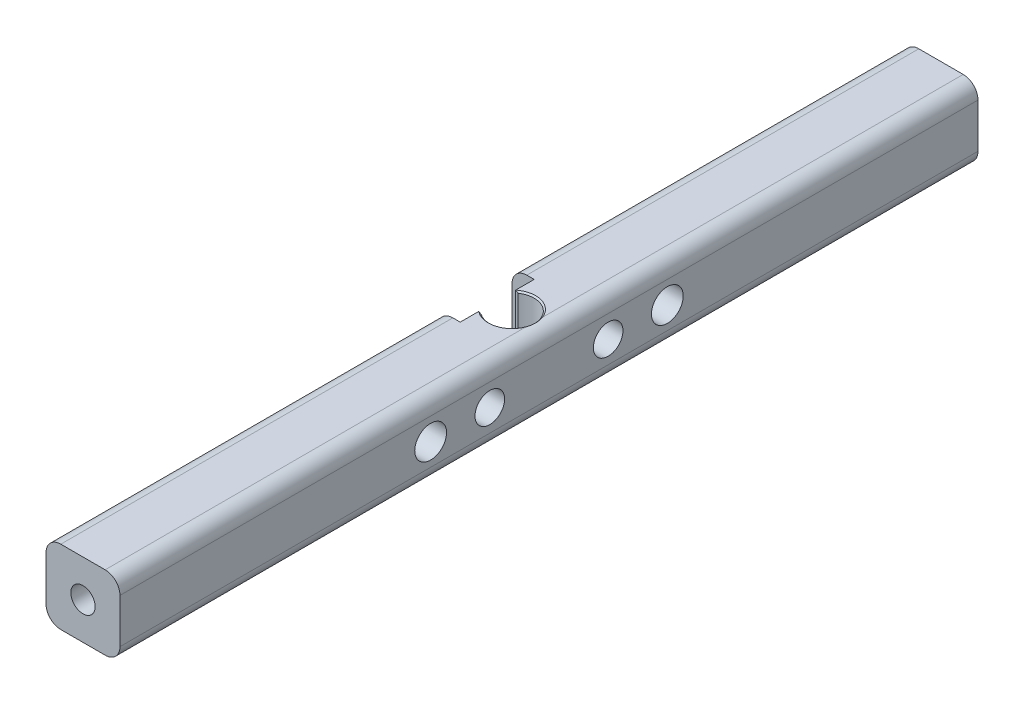
SolidWorks part; units mm, degrees
material "Alliage 1060"
ref_plane "Face" through (0, 0, 0) normal (0, 0, 1) x (1, 0, 0)
ref_plane "Dessus" through (0, 0, 0) normal (0, 1, 0) x (1, 0, 0)
ref_plane "Droite" through (0, 0, 0) normal (1, 0, 0) x (0, 0, -1)
sketch "Esquisse1" plane through (0, 0, 0) normal (0, 0, 1) x (1, 0, 0)
  line L1 (-5, 5) -> (5, 5)
  line L2 (-5, 5) -> (-5, -5)
  line L3 (-5, -5) -> (5, -5)
  line L4 (5, 5) -> (5, -5)
  dimension "D1" = 5
  dimension "D2" = 5
extrude "Boss.-Extru.1" add sketch "Esquisse1" along normal mid plane 116
sketch "Esquisse12" plane through (0, 5, 0) normal (0, 1, 0) x (1, 0, 0)
  circle A0 centre (0, 0) radius 3
extrude "Enlèv. mat.-Extru.2" cut sketch "Esquisse12" against normal up to next
chamfer "Chanfrein1" distance 0.2 angle 45 2 edges at (-3, 5, 0) (0, -5, 3)
fillet "Congé1" radius 2 4 edges at (-5, -5, 0) (5, -5, 0) (5, 5, 0) (-5, 5, 0)
hole_wizard "Trou taraudé M41" positions "Esquisse14" profile "Esquisse13" tap size "M4" standard "Iso"
sketch "Esquisse14" plane through (0, 0, 58) normal (0, 0, 1) x (1, 0, 0)
  point P0 (0, 0)
sketch "Esquisse13" plane through (0, 0, 58) normal (1, 0, 0) x (0, -1, 0)
  line L0 (0, 0) -> (0, 12.4914)
  line L1 (0, 12.4914) -> (1.65, 11.5)
  line L2 (1.65, 11.5) -> (1.65, 0)
  line L5 (1.65, 0) -> (0, 0)
  line L10 (0, 12.4914) -> (-1.65, 11.5) construction
  line L11 (0, -6.35) -> (0, 107.95) construction
  dimension "Diamètre du trou pour taraudage" = 3.3
  dimension "Profondeur du trou pour taraudage" = 11.5
  dimension "Angle de pointe" = 118
cosmetic thread "Filetage de perçage1" parameters "D1"=8, "D2"=4
hole_wizard "Trou taraudé M42" positions "Esquisse16" profile "Esquisse15" tap size "M4" standard "Iso"
sketch "Esquisse16" plane through (0, 0, -58) normal (0, 0, -1) x (-1, 0, 0)
  point P0 (0, 0)
sketch "Esquisse15" plane through (0, 0, -58) normal (1, 0, 0) x (0, 1, 0)
  line L0 (0, 0) -> (0, 12.4914)
  line L1 (0, 12.4914) -> (1.65, 11.5)
  line L2 (1.65, 11.5) -> (1.65, 0)
  line L5 (1.65, 0) -> (0, 0)
  line L10 (0, 12.4914) -> (-1.65, 11.5) construction
  line L11 (0, -6.35) -> (0, 107.95) construction
  dimension "Diamètre du trou pour taraudage" = 3.3
  dimension "Profondeur du trou pour taraudage" = 11.5
  dimension "Angle de pointe" = 118
cosmetic thread "Filetage de perçage2" parameters "D1"=8, "D2"=4
hole_wizard "Diamètre du perçage Ø5.0 (5)1" [suppressed] positions "Esquisse18" profile "Esquisse17" hole size "Ø5.0" standard "Din"
sketch "Esquisse18" plane through (-5, 0, 0) normal (-1, 0, 0) x (0, 0, 1)
  point P0 (0, 0)
sketch "Esquisse17" plane through (-5, 0, 0) normal (0, 1, 0) x (0, 0, 1)
  line L0 (0, 0) -> (0, 2)
  line L1 (0, 2) -> (2.6, 2)
  line L2 (2.6, 2) -> (2.6, 0)
  line L5 (2.6, 0) -> (0, 0)
  line L11 (0, -6.35) -> (0, 107.95) construction
  dimension "Diamètre du perçage jusqu'au prochain" = 5.2
  dimension "Profondeur du perçage jusqu'au prochain" = 2
hole_wizard "Diamètre du perçage Ø4.0 (4)1" positions "Esquisse20" profile "Esquisse19" hole size "Ø4.0" standard "Din"
sketch "Esquisse20" plane through (5, 0, 0) normal (1, 0, 0) x (0, 0, -1)
  point P0 (8, 0)
  point P2 (-8, 0)
  dimension "D1" = 8
  dimension "D2" = 8
sketch "Esquisse19" plane through (5, 0, -8) normal (0, 1, 0) x (0, 0, -1)
  line L0 (0, 0) -> (0, 6.2017)
  line L1 (0, 6.2017) -> (2, 5)
  line L2 (2, 5) -> (2, 0)
  line L5 (2, 0) -> (0, 0)
  line L10 (0, 6.2017) -> (-2, 5) construction
  line L11 (0, -6.35) -> (0, 107.95) construction
  dimension "Diamètre du perçage" = 4
  dimension "Profondeur du perçage" = 5
  dimension "Angle de pointe" = 118
hole_wizard "Chambrage pour vis à tête hexagonale M41" positions "Esquisse22" profile "Esquisse21" counterbore size "M4" standard "Iso" end condition through all
sketch "Esquisse22" plane through (-5, 0, 0) normal (-1, 0, 0) x (0, 0, 1)
  point P0 (-16, 0)
  point P2 (16, 0)
  dimension "D1" = 16
  dimension "D2" = 16
sketch "Esquisse21" plane through (-5, 0, -16) normal (0, 1, 0) x (0, 0, 1)
  line L0 (0, 0) -> (0, 10)
  line L1 (0, 10) -> (2.15, 10)
  line L3 (2.15, 10) -> (2.15, 4.4)
  line L4 (2.15, 4.4) -> (4, 4.4)
  line L5 (4, 4.4) -> (4, 0)
  line L7 (4, 0) -> (0, 0)
  line L11 (0, -6.35) -> (0, 107.95) construction
  dimension "Diamètre du perçage jusqu'au prochain" = 4.3
  dimension "Profondeur du perçage jusqu'au prochain" = 10
  dimension "Diamètre du chambrage" = 8
  dimension "Profondeur du chambrage" = 4.4
hole_wizard "Trou taraudé M31" positions "Esquisse24" profile "Esquisse23" tap size "M3" standard "Iso"
sketch "Esquisse24" plane through (-5, 0, 0) normal (-1, 0, 0) x (0, 0, 1)
  point P0 (-8, 0)
  point P2 (8, 0)
  dimension "D1" = 8
  dimension "D2" = 8
cosmetic thread "Filetage de perçage3" parameters "D1"=6, "D2"=3
cosmetic thread "Filetage de perçage4" parameters "D1"=6, "D2"=3
sketch "Esquisse23" plane through (-5, 0, -8) normal (0, 1, 0) x (0, 0, 1)
  line L0 (0, 0) -> (0, 9.2511)
  line L1 (0, 9.2511) -> (1.25, 8.5)
  line L2 (1.25, 8.5) -> (1.25, 0)
  line L5 (1.25, 0) -> (0, 0)
  line L10 (0, 9.2511) -> (-1.25, 8.5) construction
  line L11 (0, -6.35) -> (0, 107.95) construction
  dimension "Diamètre du trou pour taraudage" = 2.5
  dimension "Profondeur du trou pour taraudage" = 8.5
  dimension "Angle de pointe" = 118
sketch "Esquisse25" plane through (-5, 0, 0) normal (-1, 0, 0) x (0, 0, 1)
  line L1 (-5, 10) -> (5, 10)
  line L2 (-5, 10) -> (-5, -10)
  line L3 (-5, -10) -> (5, -10)
  line L4 (5, 10) -> (5, -10)
  dimension "D1" = 5
  dimension "D2" = 10
extrude "Enlèv. mat.-Extru.4" cut sketch "Esquisse25" against normal blind 3
sketch "Esquisse26" plane through (0, 5, 0) normal (0, 1, 0) x (1, 0, 0)
  line L1 (0, -2.5) -> (-5, -2.5)
  line L2 (0, -2.5) -> (0, 2.5)
  line L3 (0, 2.5) -> (-5, 2.5)
  line L4 (-5, -2.5) -> (-5, 2.5)
  dimension "D1" = 2.5
  dimension "D2" = 2.5
extrude "Casser Angle" cut sketch "Esquisse26" against normal up to next
